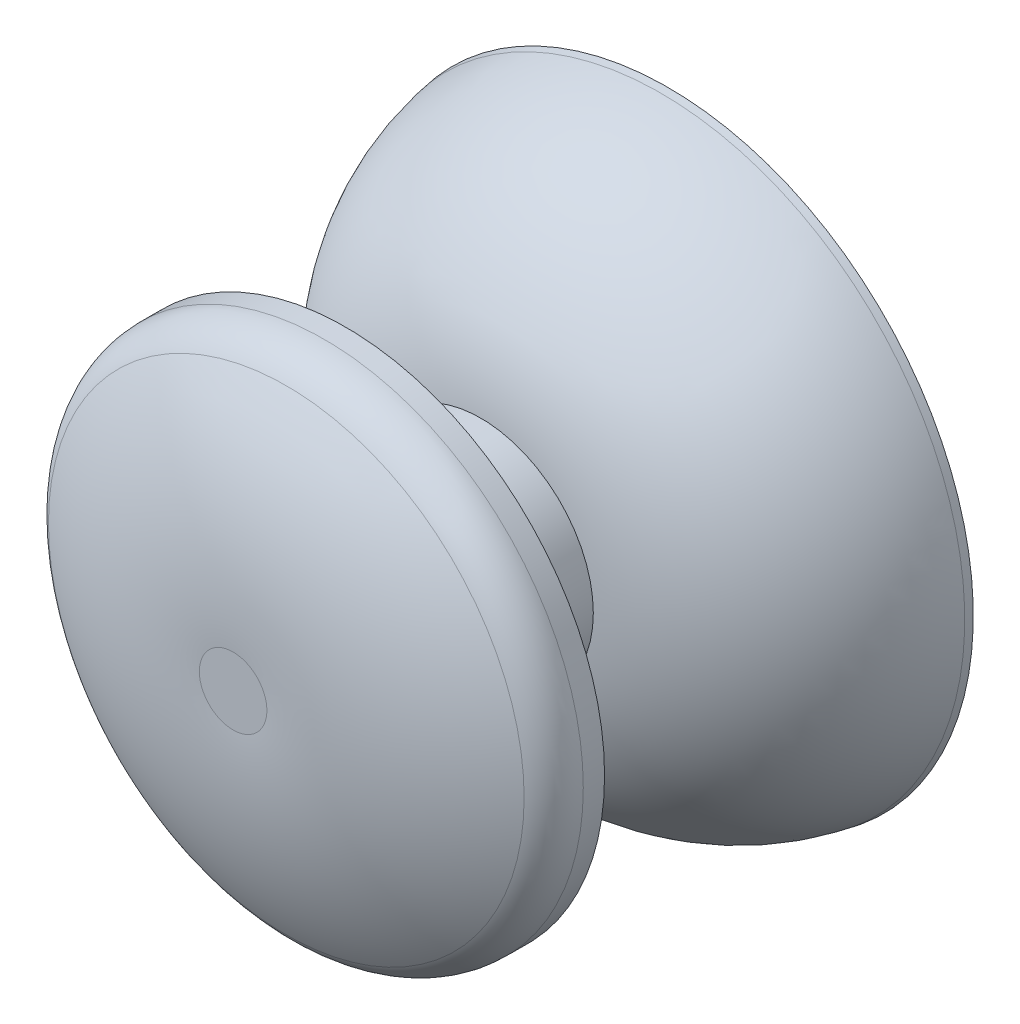
SolidWorks part; units mm, degrees
ref_plane "정면" through (0, 0, 0) normal (0, 0, 1) x (1, 0, 0)
ref_plane "윗면" through (0, 0, 0) normal (0, 1, 0) x (1, 0, 0)
ref_plane "우측면" through (0, 0, 0) normal (1, 0, 0) x (0, 0, -1)
ref_plane "평면1" through (0, 12.3611, 0) normal (0, -1, 0) x (1, 0, 0)
sketch "스케치1" plane through (0, 12.3611, 0) normal (0, -1, 0) x (1, 0, 0)
  line L0 (56.7886, 33.75) -> (55.2886, 33.75)
  line L1 (55.2886, 33.75) -> (55.2886, 24.5842)
  line L2 (55.2886, 24.5842) -> (56.9024, 24.5842)
  line L3 (56.9024, 24.5842) -> (56.9024, 19.6671)
  line L4 (56.9024, 19.6671) -> (64.1107, 19.6671)
  line L5 (67.2602, 14.75) -> (67.3296, 14.4243)
  line L6 (67.3296, 14.4243) -> (68.8424, 14.4243)
  line L7 (68.8424, 14.4243) -> (68.7886, 14.75)
  line L8 (60.2886, 22.75) -> (60.2886, 28.75)
  line L9 (60.2886, 28.75) -> (66.7886, 28.75)
  line L10 (66.7886, 28.75) -> (66.7886, 29.695)
  line L11 (55.2886, 33.7708) -> (55.2886, 14.4243) construction
  arc A0 (64.1107, 19.6671) -> (67.2602, 14.75) centre (59.1451, 13.0194) cw
  arc A1 (68.7886, 14.75) -> (60.2886, 22.75) centre (59.1451, 13.0194) ccw
  arc A2 (66.7886, 29.695) -> (65.8536, 31.3879) centre (64.7886, 29.695) ccw
  arc A3 (65.8536, 31.3879) -> (56.7886, 33.75) centre (57.5913, 18.2553) ccw
revolve "회전1" add sketch "스케치1" angle 360 about L11 reverse direction yes
